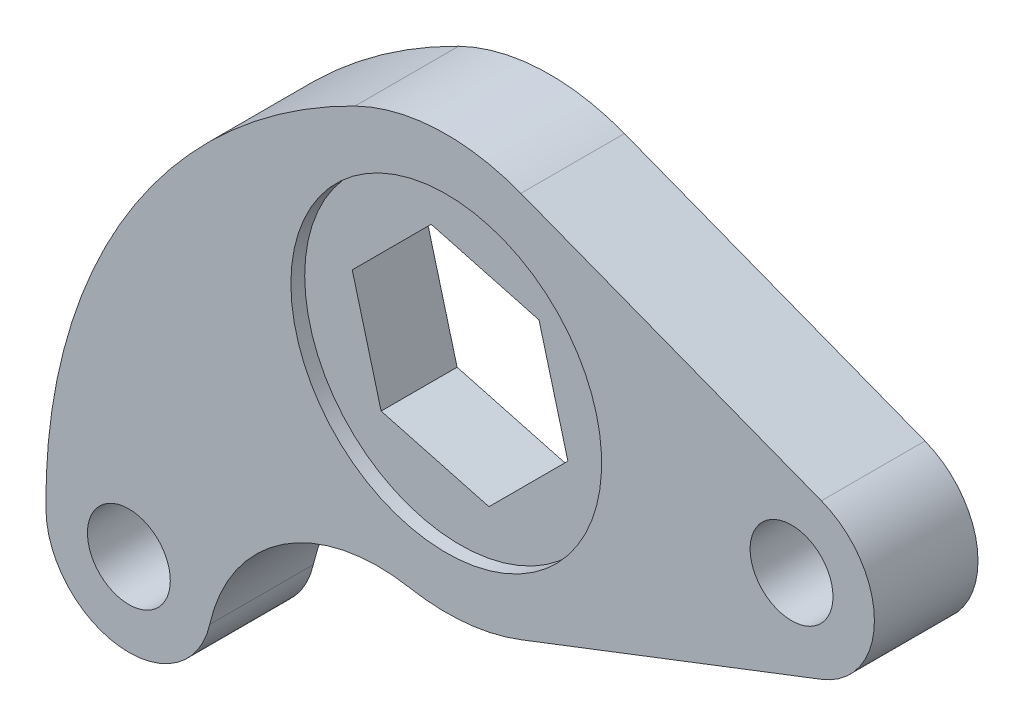
SolidWorks part; units mm, degrees
ref_plane "前基準面" through (0, 0, 0) normal (0, 0, 1) x (1, 0, 0)
ref_plane "上基準面" through (0, 0, 0) normal (0, 1, 0) x (1, 0, 0)
ref_plane "右基準面" through (0, 0, 0) normal (1, 0, 0) x (0, 0, -1)
sketch "草圖1" plane through (0, 0, 0) normal (0, 0, 1) x (1, 0, 0)
  line L0 (10.8, 27.9886) -> (54.32, 11.1954)
  line L1 (54.32, -11.1954) -> (10.8, -27.9886)
  line L2 (0, 0) -> (0, 53.055) construction
  line L3 (15.615, -4.184) -> (11.431, 11.431)
  line L4 (11.431, 11.431) -> (-4.184, 15.615)
  line L5 (-4.184, 15.615) -> (-15.615, 4.184)
  line L6 (-15.615, 4.184) -> (-11.431, -11.431)
  line L7 (-11.431, -11.431) -> (4.184, -15.615)
  line L8 (4.184, -15.615) -> (15.615, -4.184)
  line L9 (0, 0) -> (-4.184, 15.615) construction
  line L10 (0, 0) -> (-45.9619, -45.9619) construction
  line L11 (0, 0) -> (50, 0) construction
  circle A1 centre (0, 0) radius 30 construction
  arc A2 (-13.2177, 26.9312) -> (10.8, 27.9886) centre (0, 0) cw
  arc A3 (-5.3834, -29.513) -> (10.8, -27.9886) centre (0, 0) ccw
  circle A4 centre (50, 0) radius 6
  arc A5 (54.32, 11.1954) -> (54.32, -11.1954) centre (50, 0) cw
  circle A6 centre (-45.9619, -45.9619) radius 6
  arc A7 (-57.9604, -46.1519) -> (-34.2563, -48.6037) centre (-45.9619, -45.9619) ccw
  arc A8 (-57.9604, -46.1519) -> (-13.2177, 26.9312) centre (22.0295, -44.8854) cw
  circle A9 centre (0, 0) radius 14 construction
  arc A10 (-34.2563, -48.6037) -> (-5.3834, -29.513) centre (-9.8696, -54.1072) cw
  dimension "D2" = 30
  dimension "D3" = 50
  dimension "D4" = 12
  dimension "D5" = 12
  dimension "D6" = 12
  dimension "D7" = 12
  dimension "D11" = 80
  dimension "D12" = 135
  dimension "25" = 25
  dimension "D8" = 28
  dimension "D9" = 15
  dimension "D10" = 65
extrude "填料-伸長2" add sketch "草圖1" along normal mid plane 15
sketch "草圖4" plane through (0, 0, 0) normal (0, 0, 1) x (1, 0, 0)
  circle A0 centre (0, 0) radius 22.5
  dimension "D1" = 45
extrude "除料-伸長4" cut sketch "草圖4" along normal blind 2 from surface starting at face at (56, 0, -7.5)
extrude "除料-伸長5" cut sketch "草圖4<2>" against normal blind 2 from surface starting at face at (-39.9619, -45.9619, 7.5)
sketch "草圖4<2>" plane through (0, 0, 0) normal (0, 0, 1) x (1, 0, 0) same geometry as "草圖4"
